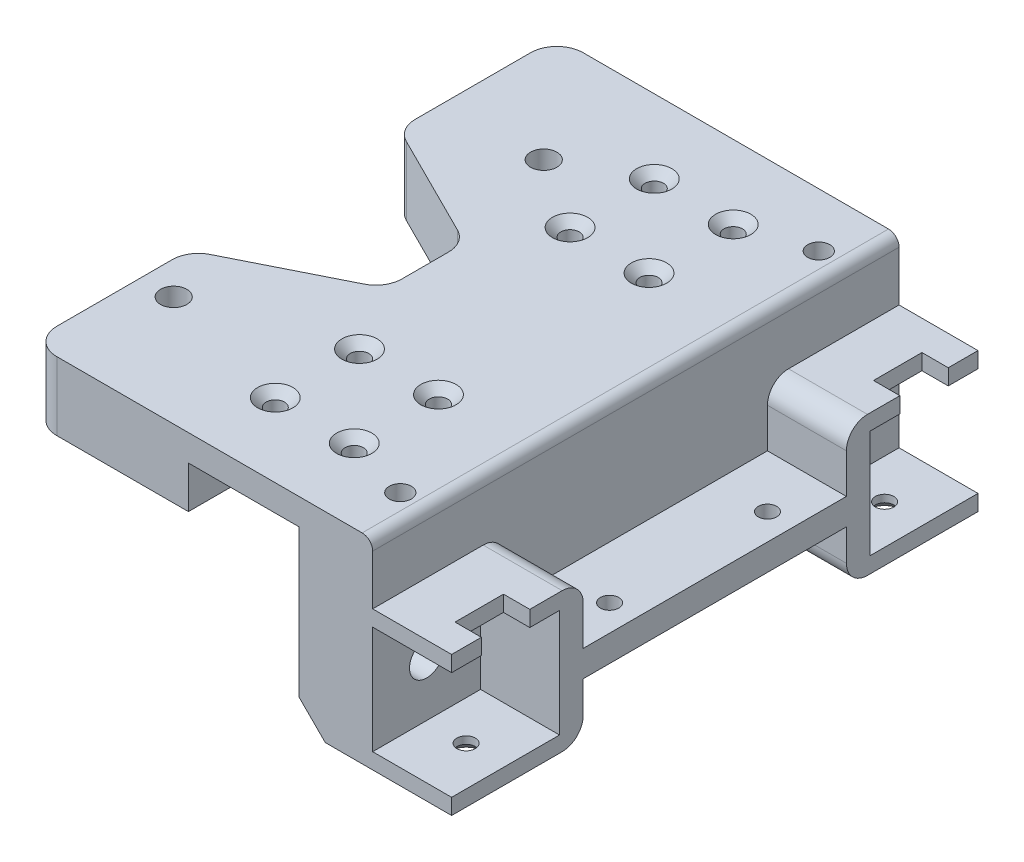
SolidWorks part; units mm, degrees
ref_plane "Front Plane" through (0, 0, 0) normal (0, 0, 1) x (1, 0, 0)
ref_plane "Top Plane" through (0, 0, 0) normal (0, 1, 0) x (1, 0, 0)
ref_plane "Right Plane" through (0, 0, 0) normal (1, 0, 0) x (0, 0, -1)
sketch "Sketch1" plane through (0, 0, 0) normal (0, 1, 0) x (1, 0, 0)
  line L0 (0, 50) -> (0, -50) construction
  line L1 (-10, 50) -> (10, 50)
  line L2 (-10, 50) -> (-10, -50)
  line L3 (-10, -50) -> (10, -50)
  line L4 (10, 50) -> (10, -50) construction
  line L5 (-10, 50) -> (10, -50) construction
  line L6 (-10, -50) -> (10, 50) construction
  line L7 (-7.5, 36) -> (7.5, 36) construction
  line L8 (-7.5, 36) -> (7.5, 20) construction
  line L9 (-10, 0) -> (10, 0) construction
  line L10 (-7.5, -36) -> (7.5, -20) construction
  line L11 (-7.5, -36) -> (7.5, -36) construction
  line L12 (-7.5, 20) -> (7.5, 20) construction
  line L13 (10, 50) -> (11, 50)
  line L14 (11, 50) -> (11, -50)
  line L15 (11, -50) -> (10, -50)
  circle A0 centre (-7.5, 36) radius 1.75
  circle A1 centre (7.5, 36) radius 1.75
  circle A2 centre (-7.5, 20) radius 1.75
  circle A3 centre (7.5, 20) radius 1.75
  circle A4 centre (7.5, -20) radius 1.75
  circle A5 centre (-7.5, -20) radius 1.75
  circle A6 centre (7.5, -36) radius 1.75
  circle A7 centre (-7.5, -36) radius 1.75
  point P0 (0, 0)
  point P16 (0, 36)
  dimension "D2" = 3.5
  dimension "D1" = 20
  dimension "D3" = 15
  dimension "D4" = 16
  dimension "D5" = 100
  dimension "D6" = 20
  dimension "D7" = 1
extrude "Boss-Extrude1" add sketch "Sketch1" along normal blind 5
sketch "Sketch2" plane through (11, 0, 0) normal (1, 0, 0) x (0, 0, -1)
  line L1 (-50, 5) -> (50, 5)
  line L2 (-50, 5) -> (-50, -33)
  line L3 (-50, -33) -> (50, -33)
  line L5 (50, 5) -> (50, -33)
  line L6 (50, 5) -> (50, 0) construction
  line L7 (-50, 5) -> (-50, 0) construction
  line L8 (-50, 5) -> (50, 5) construction
  dimension "D1" = 38
extrude "Boss-Extrude2" add sketch "Sketch2" along normal blind 14
sketch "Sketch3" plane through (25, 0, 0) normal (1, 0, 0) x (0, 0, -1)
  line L0 (0, 5) -> (0, -33) construction
  line L1 (-25, -18) -> (25, -18)
  line L2 (-25, -18) -> (-25, -23)
  line L3 (-25, -23) -> (25, -23)
  line L4 (25, -18) -> (25, -23)
  line L5 (50, 5) -> (-50, 5) construction
  line L6 (-50, -33) -> (50, -33) construction
  point P10 (0, -18)
  dimension "D1" = 5
  dimension "D2" = 50
  dimension "D3" = 10
extrude "Boss-Extrude3" add sketch "Sketch3" along normal blind 15
sketch "Sketch4" plane through (0, -18, 0) normal (0, 1, 0) x (1, 0, 0)
  line L0 (30, 0) -> (40, 0) construction
  line L2 (40, 25) -> (40, -25) construction
  line L3 (35, -15) -> (35, 15) construction
  circle A0 centre (35, 15) radius 1.75
  circle A1 centre (35, -15) radius 1.75
  point P8 (35, 0)
  point P11 (0, 0)
  dimension "D1" = 30
  dimension "D2" = 3.5
  dimension "D3" = 10
extrude "Cut-Extrude1" cut sketch "Sketch4" against normal through all
sketch "Sketch8" plane through (25, 0, 0) normal (1, 0, 0) x (0, 0, -1)
  line L0 (-50, 5) -> (-50, -33) construction
  line L1 (-50, -6.5) -> (-25, -6.5)
  line L2 (-50, -6.5) -> (-50, -9.5)
  line L3 (-50, -33) -> (-25, -33)
  line L4 (-25, -6.5) -> (-25, -33)
  line L5 (-50, -30) -> (-50, -33)
  line L6 (-50, -30) -> (-29.5, -30)
  line L8 (-50, -9.5) -> (-29.5, -9.5)
  line L9 (-29.5, -30) -> (-29.5, -9.5)
  line L10 (0, 20.9) -> (0, -20.9) construction
  line L11 (29.5, -30) -> (29.5, -9.5)
  line L12 (50, -9.5) -> (29.5, -9.5)
  line L13 (50, -30) -> (29.5, -30)
  line L14 (50, -30) -> (50, -33)
  line L15 (25, -6.5) -> (25, -33)
  line L16 (50, -33) -> (25, -33)
  line L17 (50, -6.5) -> (50, -9.5)
  line L18 (50, -6.5) -> (25, -6.5)
  line L19 (-50, -33) -> (50, -33) construction
  line L20 (-25, -18) -> (-25, -23) construction
  dimension "D1" = 3
  dimension "D3" = 3
  dimension "D4" = 20.5
  dimension "D5" = 20.5
extrude "Boss-Extrude6" add sketch "Sketch8" along normal blind 15
sketch "Sketch9" plane through (25, 0, 0) normal (1, 0, 0) x (0, 0, -1)
  line L0 (-50, -9.5) -> (-29.5, -30) construction
  line L1 (50, -9.5) -> (29.5, -30) construction
  circle A0 centre (-39.75, -19.75) radius 3.25
  circle A1 centre (39.75, -19.75) radius 3.25
  dimension "D1" = 6.5
extrude "Cut-Extrude3" cut sketch "Sketch9" against normal through all
sketch "Sketch10" plane through (11, 0, 0) normal (-1, 0, 0) x (0, 0, 1)
  circle A0 centre (-39.75, -19.75) radius 5.25
  circle A1 centre (39.75, -19.75) radius 5.25
  dimension "D1" = 10.5
extrude "Cut-Extrude4" cut sketch "Sketch10" against normal offset from surface (9 mm away) 5 up to face at (25, -19.75, 36.5)
sketch "Sketch11" plane through (0, -6.5, 0) normal (0, 1, 0) x (1, 0, 0)
  line L0 (40, -25) -> (40, -50) construction
  line L1 (40, -35.15) -> (35, -35.15)
  line L2 (40, -35.15) -> (40, -44.35)
  line L3 (40, -44.35) -> (35, -44.35)
  line L4 (35, -35.15) -> (35, -44.35)
  line L5 (35, -39.75) -> (40, -39.75) construction
  line L7 (-10, 0) -> (40, 0) construction
  line L8 (-10, 50) -> (-10, -50) construction
  line L9 (40, 25) -> (40, -25) construction
  line L10 (40, -35.15) -> (35, -35.15)
  line L11 (40, -44.35) -> (35, -44.35)
  line L12 (35, 39.75) -> (40, 39.75) construction
  line L13 (40, 44.35) -> (35, 44.35)
  line L14 (40, 35.15) -> (35, 35.15)
  line L15 (35, 35.15) -> (35, 44.35)
  line L16 (40, 44.35) -> (35, 44.35)
  line L17 (40, 35.15) -> (40, 44.35)
  line L18 (40, 35.15) -> (35, 35.15)
  line L19 (40, -50) -> (40, -29.5) construction
  point P22 (40, -39.75)
  line M7 (40, -50) -> (40, -25)
  dimension "D1" = 9.2
  dimension "D3" = 5
extrude "Cut-Extrude5" cut sketch "Sketch11" against normal up to next contours L1 L4 L3 M7 | L14 L17 L13 L15 region at (37.5, -6.5, 39.75) region at (37.5, -6.5, -39.75)
sketch "Sketch12" plane through (0, -30, 0) normal (0, 1, 0) x (1, 0, 0)
  line L0 (40, -39.75) -> (25, -39.75) construction
  line L1 (40, -29.5) -> (40, -50) construction
  line L2 (25, -25) -> (25, -50) construction
  line L3 (-20.9, 0) -> (20.9, 0) construction
  circle A0 centre (32.5, -39.75) radius 1.75
  circle A2 centre (32.5, 39.75) radius 1.75
  dimension "D1" = 3.5
extrude "Cut-Extrude6" cut sketch "Sketch12" against normal through all
sketch "Sketch13" plane through (-10, 0, 0) normal (-1, 0, 0) x (0, 0, 1)
  line L1 (-50, 5) -> (50, 5)
  line L2 (-50, 5) -> (-50, -8)
  line L3 (-50, -8) -> (50, -8)
  line L4 (50, 5) -> (50, -8)
  dimension "D1" = 13
extrude "Boss-Extrude7" add sketch "Sketch13" along normal blind 30
sketch "Sketch14" plane through (0, 5, 0) normal (0, 1, 0) x (1, 0, 0)
  line L0 (-40, -50) -> (25, -50) construction
  line L1 (-10.5, -50) -> (10.5, -50) construction
  line L2 (-10.5, -50) -> (-10.5, 50) construction
  line L3 (-10.5, 50) -> (10.5, 50) construction
  line L4 (10.5, -50) -> (10.5, 50) construction
  line L5 (25, 50) -> (-40, 50) construction
  line L6 (-27.65, 28.65) -> (-27.65, -29.07) construction
  line L12 (-33.73, -35.15) -> (40, -35.15) construction
  line L18 (-21.15, 35.15) -> (40, 35.15) construction
  circle A0 centre (-21.15, 28.65) radius 2.5
  circle A1 centre (-33.73, -29.07) radius 2.5
  circle A2 centre (-33.73, -29.07) radius 6.08 construction
  circle A3 centre (-21.15, 28.65) radius 6.5 construction
  point P14 (0, 50)
  dimension "D1" = 5
  dimension "D2" = 5
  dimension "D4" = 21
  dimension "D5" = 12.16
  dimension "D6" = 13
  dimension "D3" = 21.15
extrude "Cut-Extrude7" cut sketch "Sketch14" against normal through all
sketch "Sketch15" plane through (0, -8, 0) normal (0, -1, 0) x (1, 0, 0)
  line L0 (-40, -50) -> (-40, 50) construction
  line L1 (-29.73, 26.7606) -> (-29.73, 31.3794)
  line L2 (-29.73, 31.3794) -> (-33.73, 33.6888)
  line L3 (-33.73, 33.6888) -> (-37.73, 31.3794)
  line L4 (-37.73, 31.3794) -> (-37.73, 26.7606)
  line L5 (-37.73, 26.7606) -> (-33.73, 24.4512)
  line L6 (-33.73, 24.4512) -> (-29.73, 26.7606)
  line L7 (-25.15, -30.9594) -> (-21.15, -33.2688)
  line L8 (-21.15, -33.2688) -> (-17.15, -30.9594)
  line L9 (-17.15, -30.9594) -> (-17.15, -26.3406)
  line L10 (-17.15, -26.3406) -> (-21.15, -24.0312)
  line L11 (-21.15, -24.0312) -> (-25.15, -26.3406)
  line L12 (-25.15, -26.3406) -> (-25.15, -30.9594)
  circle A0 centre (-33.73, 29.07) radius 4 construction
  circle A1 centre (-21.15, -28.65) radius 4 construction
  dimension "D1" = 8
extrude "Cut-Extrude8" cut sketch "Sketch15" against normal blind 4
sketch "Sketch16" plane through (0, 5, 0) normal (0, 1, 0) x (1, 0, 0)
  line L0 (20, 39.75) -> (40, 39.75) construction
  line L1 (40, 50) -> (40, 29.5) construction
  line L2 (20, -39.75) -> (40, -39.75) construction
  line L3 (40, -29.5) -> (40, -50) construction
  circle A0 centre (20, 39.75) radius 2.1
  circle A1 centre (20, -39.75) radius 2.1
  dimension "D1" = 4.2
  dimension "D2" = 4.2
  dimension "D3" = 20
extrude "Cut-Extrude9" cut sketch "Sketch16" against normal blind 4
chamfer "Chamfer1" distance 1.6 angle 45 8 edges at (-7.5, 5, -34.25) (7.5, 5, -34.25) (-7.5, 5, -18.25) (7.5, 5, -18.25) (-7.5, 5, 18.25) (7.5, 5, 18.25) (-7.5, 5, 34.25) (7.5, 5, 34.25)
sketch "Sketch17" plane through (0, 5, 0) normal (0, 1, 0) x (1, 0, 0)
  line L0 (-40, 20) -> (-15, 7.5)
  line L1 (-40, -50) -> (-40, 50) construction
  line L2 (-15, 7.5) -> (-15, -7.5)
  line L3 (-15, -7.5) -> (-40, -20)
  line L4 (-40, -20) -> (-40, 20)
  point P6 (-15, 0)
  dimension "D1" = 15
  dimension "D2" = 40
  dimension "D3" = 15
extrude "Cut-Extrude10" cut sketch "Sketch17" against normal through all
chamfer "Chamfer2" distance 1.6 angle 45 2 edges at (32.5, -33, -41.5) (32.5, -33, 41.5)
chamfer "Chamfer3" distance 5 angle 45 1 edges at (11, -33, 0)
sketch "Sketch18" plane through (0, 1, 0) normal (0, 1, 0) x (1, 0, 0)
  circle A0 centre (20, 39.75) radius 1.75
  circle A1 centre (20, -39.75) radius 1.75
  dimension "D1" = 3.5
  dimension "D2" = 3.5
extrude "Cut-Extrude11" cut sketch "Sketch18" against normal blind 4
fillet "Fillet1" radius 5 6 edges at (-40, -1.5, -50) (-40, -1.5, 50) (-40, -1.5, 20) (-15, -1.5, 7.5) (-15, -1.5, -7.5) (-40, -1.5, -20)
fillet "Fillet2" radius 2 1 edges at (25, 5, 0)
fillet "Fillet3" radius 4 4 edges at (32.5, -33, -25) (32.5, -6.5, -25) (32.5, -6.5, 25) (32.5, -33, 25)
